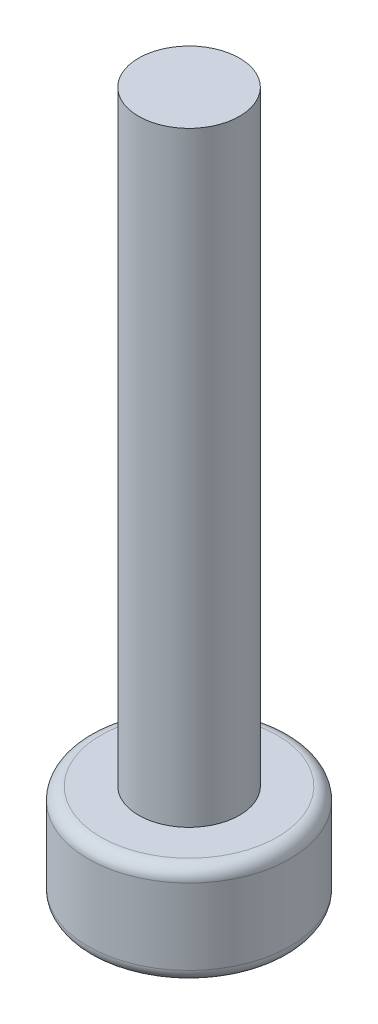
SolidWorks part; units mm, degrees
material "AISI 304"
ref_plane "Front Plane" through (0, 0, 0) normal (0, 0, 1) x (1, 0, 0)
ref_plane "Top Plane" through (0, 0, 0) normal (0, 1, 0) x (1, 0, 0)
ref_plane "Right Plane" through (0, 0, 0) normal (1, 0, 0) x (0, 0, -1)
sketch "Sketch1" plane through (0, 0, 0) normal (0, 1, 0) x (1, 0, 0)
  circle A0 centre (0, 0) radius 1
  circle A1 centre (0, 0) radius 2
  dimension "D1" = 2
  dimension "D2" = 4
extrude "Boss-Extrude1" add sketch "Sketch1" along normal blind 12 contours A0
extrude "Boss-Extrude2" add sketch "Sketch1<3>" against normal blind 2 contours A0 | A1 A0 region at (0, 0, 0) region at (-1.9434, 0, 0)
sketch "Sketch1<3>" plane through (0, 0, 0) normal (0, 1, 0) x (1, 0, 0) same geometry as "Sketch1"
sketch "Sketch2" plane through (0, -2, 0) normal (0, -1, 0) x (1, 0, 0)
  line L1 (0, 0.866) -> (-0.75, 0.433)
  line L2 (-0.75, 0.433) -> (-0.75, -0.433)
  line L3 (-0.75, -0.433) -> (0, -0.866)
  line L4 (0, -0.866) -> (0.75, -0.433)
  line L5 (0.75, -0.433) -> (0.75, 0.433)
  line L6 (0.75, 0.433) -> (0, 0.866)
  circle A0 centre (0, 0) radius 0.75 construction
  point P1 (0, 0)
  dimension "D1" = 1.5
extrude "Cut-Extrude1" cut sketch "Sketch2" against normal blind 2
fillet "Fillet1" radius 0.25 2 edges at (0, 0, 2) (0, -2, 2)
